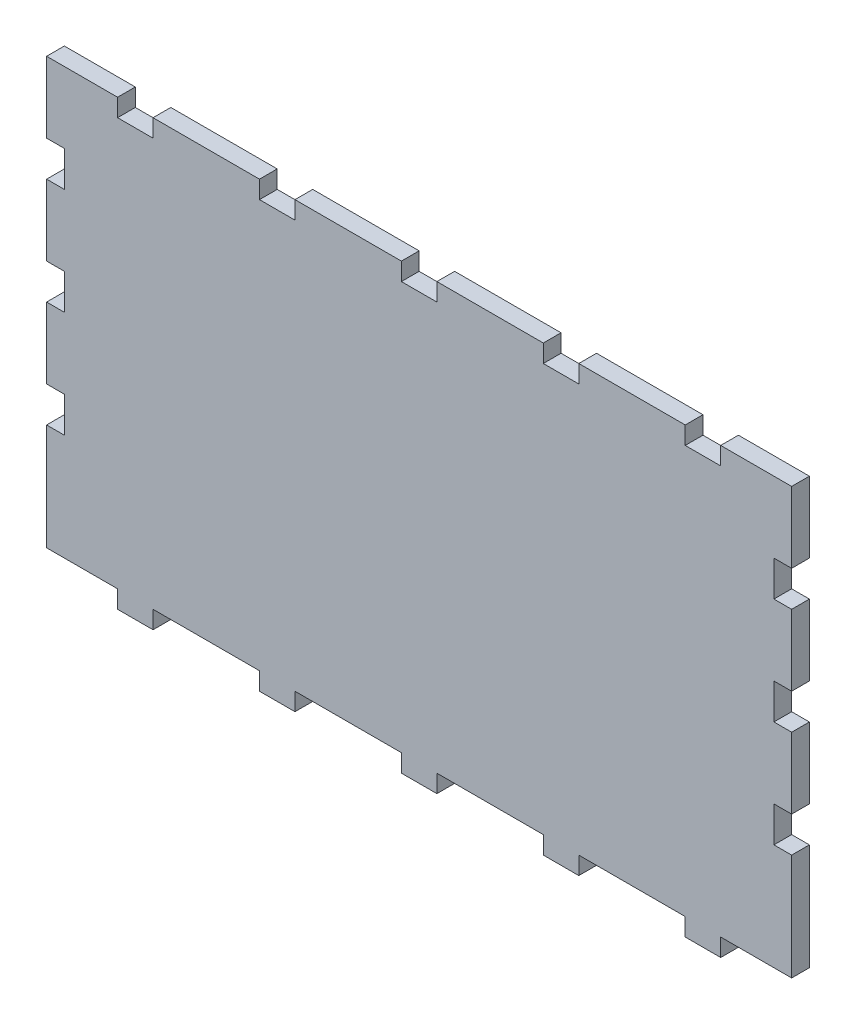
SolidWorks part; units mm, degrees
ref_plane "Ön Düzlem" through (0, 0, 0) normal (0, 0, 1) x (1, 0, 0)
ref_plane "Üst Düzlem" through (0, 0, 0) normal (0, 1, 0) x (1, 0, 0)
ref_plane "Sağ Düzlem" through (0, 0, 0) normal (1, 0, 0) x (0, 0, -1)
sketch "Sketch1" plane through (0, 0, 0) normal (0, 0, 1) x (1, 0, 0)
  line L0 (-85, 60) -> (-85, 55)
  line L1 (-105, -60) -> (-85, -60)
  line L2 (-105, -60) -> (-105, -30)
  line L3 (-105, 60) -> (-85, 60)
  line L4 (105, -60) -> (105, -30)
  line L5 (-105, -60) -> (105, 60) construction
  line L6 (-105, 60) -> (105, -60) construction
  line L7 (-85, 55) -> (-75, 55)
  line L8 (-75, 55) -> (-75, 60)
  line L9 (-45, 60) -> (-45, 55)
  line L10 (-35, 55) -> (-35, 60)
  line L11 (-45, 55) -> (-35, 55)
  line L12 (-5, 60) -> (-5, 55)
  line L13 (5, 55) -> (5, 60)
  line L14 (-5, 55) -> (5, 55)
  line L15 (35, 60) -> (35, 55)
  line L16 (45, 55) -> (45, 60)
  line L17 (35, 55) -> (45, 55)
  line L18 (75, 60) -> (75, 55)
  line L19 (85, 55) -> (85, 60)
  line L20 (75, 55) -> (85, 55)
  line L21 (-75, 60) -> (-45, 60)
  line L22 (-35, 60) -> (-5, 60)
  line L23 (5, 60) -> (35, 60)
  line L24 (45, 60) -> (75, 60)
  line L25 (85, 60) -> (105, 60)
  line L26 (-105, 0) -> (105, 0) construction
  line L27 (0, -53.6405) -> (0, 53.6405) construction
  line L28 (-105, 40) -> (-100, 40)
  line L29 (-100, 40) -> (-100, 30)
  line L30 (-100, 30) -> (-105, 30)
  line L31 (-100, 0) -> (-105, 0)
  line L32 (-105, 10) -> (-100, 10)
  line L33 (-100, 10) -> (-100, 0)
  line L34 (-100, -30) -> (-105, -30)
  line L35 (-105, -20) -> (-100, -20)
  line L36 (-100, -20) -> (-100, -30)
  line L37 (100, 30) -> (105, 30)
  line L38 (105, 40) -> (100, 40)
  line L39 (100, 40) -> (100, 30)
  line L40 (105, 10) -> (100, 10)
  line L41 (100, 10) -> (100, 0)
  line L42 (100, 0) -> (105, 0)
  line L43 (105, -20) -> (100, -20)
  line L44 (100, -20) -> (100, -30)
  line L45 (100, -30) -> (105, -30)
  line L46 (85, -65) -> (85, -60)
  line L47 (75, -65) -> (85, -65)
  line L48 (75, -60) -> (75, -65)
  line L49 (45, -65) -> (45, -60)
  line L50 (35, -65) -> (45, -65)
  line L51 (35, -60) -> (35, -65)
  line L52 (5, -65) -> (5, -60)
  line L53 (-5, -65) -> (5, -65)
  line L55 (-35, -65) -> (-35, -60)
  line L56 (-45, -65) -> (-35, -65)
  line L57 (-45, -60) -> (-45, -65)
  line L58 (-75, -65) -> (-75, -60)
  line L59 (-85, -65) -> (-75, -65)
  line L60 (-85, -60) -> (-85, -65)
  line L61 (-75, -60) -> (-45, -60)
  line L63 (5, -60) -> (35, -60)
  line L64 (45, -60) -> (75, -60)
  line L65 (85, -60) -> (105, -60)
  line L66 (-105, -20) -> (-105, 0)
  line L67 (-105, 10) -> (-105, 30)
  line L68 (-105, 40) -> (-105, 60)
  line L69 (105, 40) -> (105, 60)
  line L70 (105, 10) -> (105, 30)
  line L71 (105, -20) -> (105, 0)
  line L72 (-35, -60) -> (-5, -60)
  line L73 (-5, -65) -> (-5, -60)
  circle A1 centre (-30, 0) radius 45 construction
  point P0 (0, 0)
  point P7 (80.0391, -60.7455)
  point P9 (34.0908, -60.6635)
  dimension "D3" = 10
  dimension "D5" = 90
  dimension "D6" = 5
  dimension "D1" = 120
  dimension "D2" = 210
  dimension "D4" = 30
  dimension "D7" = 10
  dimension "D8" = 5
  dimension "D9" = 20
  dimension "D11" = 30
  dimension "D12" = 5
  dimension "D13" = 10
  dimension "D14" = 20
  dimension "D16" = 20
  dimension "D17" = 30
  dimension "D18" = 30
  dimension "D20" = 20
  dimension "D10" = 5
  dimension "D15" = 3
extrude "Boss-Extrude1" add sketch "Sketch1" along normal blind 5
